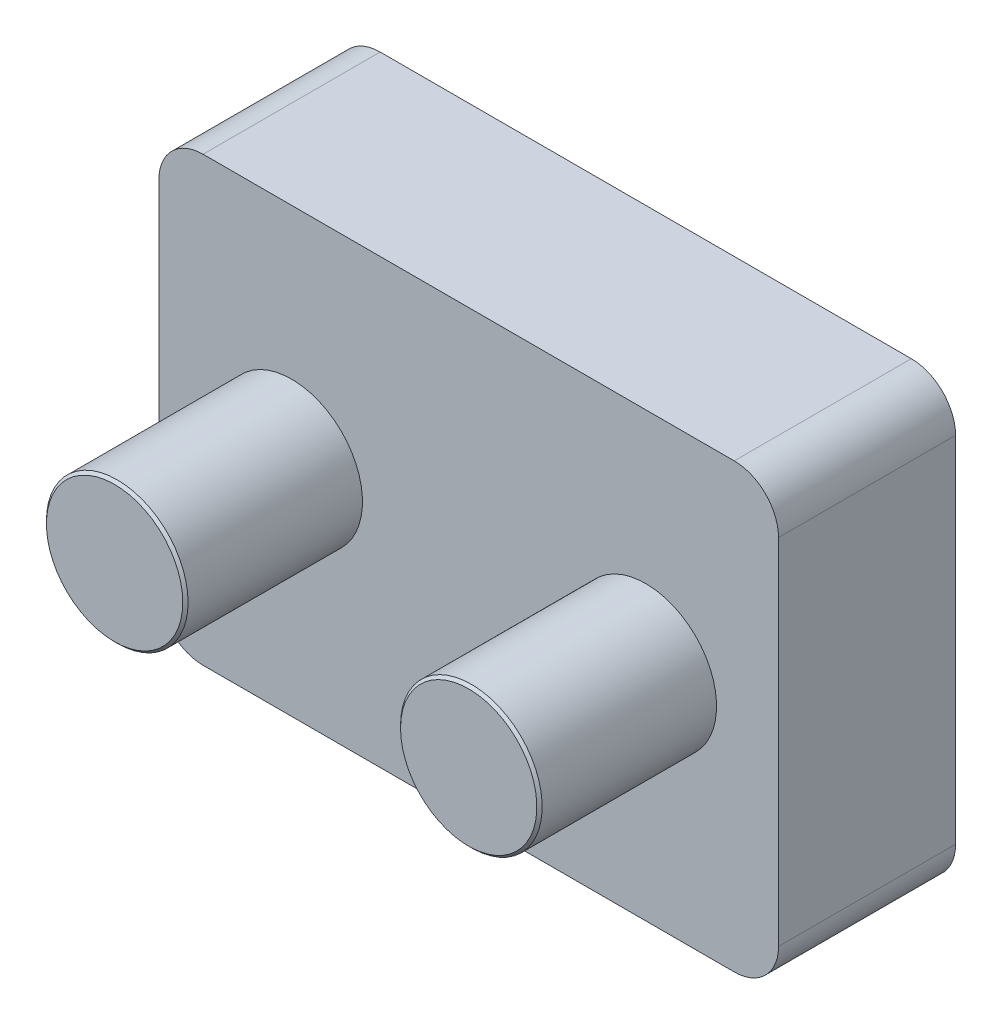
SolidWorks part; units mm, degrees
material "Полиамид П-12Б-20 ТУ 6-05-988-87"
ref_plane "Спереди" through (0, 0, 0) normal (0, 0, 1) x (1, 0, 0)
ref_plane "Сверху" through (0, 0, 0) normal (0, 1, 0) x (1, 0, 0)
ref_plane "Справа" through (0, 0, 0) normal (1, 0, 0) x (0, 0, -1)
ref_axis "ОсьX" through (-88.99, 0, 0) along (1, 0, 0)
ref_axis "ОсьZ" through (0, 55, 0) along (0, -1, 0)
ref_axis "ОсьY" through (0, 0, -88.99) along (0, 0, 1)
sketch "Эскиз1" plane through (0, 0, 0) normal (0, 0, 1) x (1, 0, 0)
  line L1 (35, 25) -> (-35, 25)
  line L2 (35, 25) -> (35, -25)
  line L3 (35, -25) -> (-35, -25)
  line L4 (-35, 25) -> (-35, -25)
  line L5 (35, 25) -> (-35, -25) construction
  line L6 (35, -25) -> (-35, 25) construction
  point P0 (0, 0)
  dimension "D1" = 50
  dimension "D2" = 70
extrude "Бобышка-Вытянуть1" add sketch "Эскиз1" along normal blind 20
sketch "Эскиз2" plane through (0, 0, 20) normal (0, 0, 1) x (1, 0, 0)
  line L0 (0, 20.7712) -> (0, -20.5914) construction
  circle A0 centre (-20, 0) radius 8
  circle A1 centre (20, 0) radius 8
  dimension "D1" = 16
  dimension "D2" = 40
extrude "Бобышка-Вытянуть2" add sketch "Эскиз2" along normal blind 20
chamfer "Фаска1" distance 0.3 angle 45 2 edges at (12, 0, 40) (-12, 0, 40)
fillet "Скругление1" radius 5 4 edges at (-35, -25, 10) (35, -25, 10) (35, 25, 10) (-35, 25, 10)
